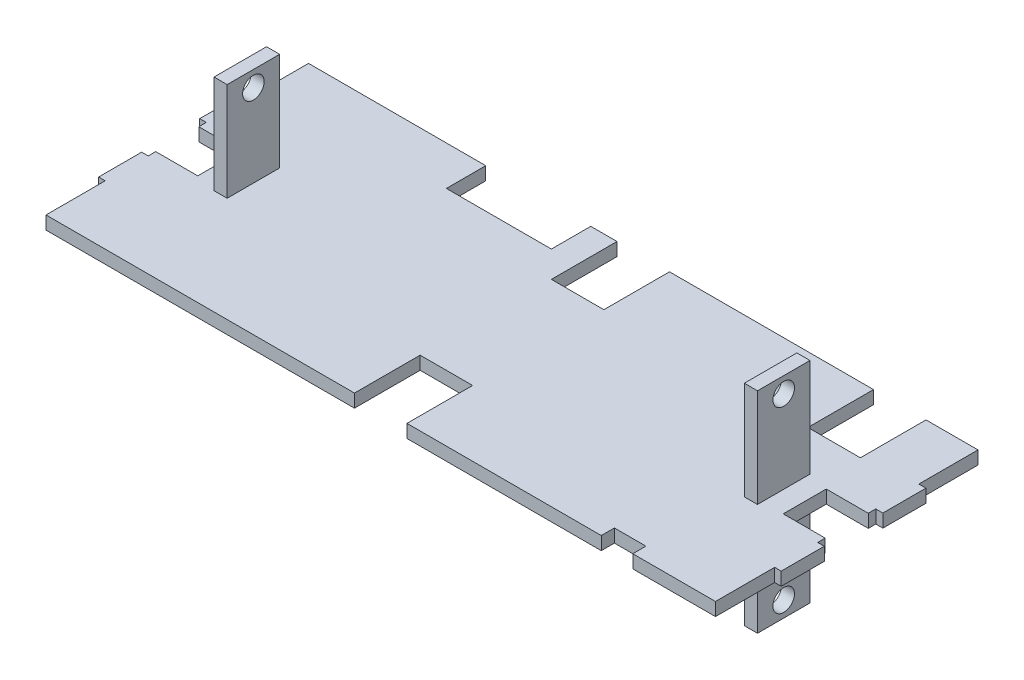
SolidWorks part; units mm, degrees
ref_plane "Front Plane" through (0, 0, 0) normal (0, 0, 1) x (1, 0, 0)
ref_plane "Top Plane" through (0, 0, 0) normal (0, 1, 0) x (1, 0, 0)
ref_plane "Right Plane" through (0, 0, 0) normal (1, 0, 0) x (0, 0, -1)
sketch "Sketch1" plane through (0, 0, 0) normal (0, 1, 0) x (1, 0, 0)
  line L0 (-136.779, 63.5) -> (-111.379, 63.5)
  line L1 (161.925, -63.5) -> (121.92, -63.5)
  line L2 (161.925, -63.5) -> (161.925, -34.8747)
  line L3 (161.925, 63.5) -> (136.779, 63.5)
  line L4 (-161.925, -63.5) -> (-161.925, -34.8747)
  line L5 (161.925, -63.5) -> (-161.925, 63.5) construction
  line L6 (161.925, 63.5) -> (-161.925, -63.5) construction
  line L7 (161.925, 10.414) -> (141.605, 10.414)
  line L9 (161.925, -10.414) -> (141.605, -10.414)
  line L10 (141.605, 10.414) -> (141.605, -10.414)
  line L11 (-136.779, 63.5) -> (-161.925, 63.5)
  line L13 (-161.925, -10.414) -> (-141.605, -10.414)
  line L14 (-141.605, 10.414) -> (-141.605, -10.414)
  line L15 (-161.925, 10.414) -> (-141.605, 10.414)
  line L17 (-141.605, 0) -> (127, 0) construction
  line L18 (-161.925, 14.0467) -> (-165.1, 14.0467)
  line L20 (-161.925, 34.8747) -> (-165.1, 34.8747)
  line L21 (-165.1, 14.0467) -> (-165.1, 34.8747)
  line L22 (-161.925, -34.8747) -> (-165.1, -34.8747)
  line L23 (-165.1, -14.0467) -> (-165.1, -34.8747)
  line L24 (-161.925, -14.0467) -> (-165.1, -14.0467)
  line L27 (161.925, -14.0467) -> (165.1, -14.0467)
  line L28 (165.1, -14.0467) -> (165.1, -34.8747)
  line L29 (161.925, -34.8747) -> (165.1, -34.8747)
  line L30 (161.925, 34.8747) -> (165.354, 34.8747)
  line L31 (165.354, 14.0467) -> (165.354, 34.8747)
  line L32 (161.925, 14.0467) -> (165.354, 14.0467)
  line L34 (-161.925, 34.8747) -> (-161.925, 63.5)
  line L35 (-161.925, -14.0467) -> (-161.925, -10.414)
  line L36 (161.925, 34.8747) -> (161.925, 63.5)
  line L37 (161.925, -14.0467) -> (161.925, -10.414)
  line L38 (-161.925, 10.414) -> (-161.925, 14.0467)
  line L39 (161.925, 10.414) -> (161.925, 14.0467)
  line L44 (111.379, 63.5) -> (111.379, 31.75)
  line L45 (111.379, 31.75) -> (136.779, 31.75)
  line L46 (136.779, 63.5) -> (136.779, 31.75)
  line L47 (111.379, 63.5) -> (12.7, 63.5)
  line L48 (106.68, -63.5) -> (12.7, -63.5)
  line L50 (106.68, -63.5) -> (106.68, -57.15)
  line L51 (106.68, -57.15) -> (121.92, -57.15)
  line L52 (121.92, -63.5) -> (121.92, -57.15)
  line L56 (-135.9408, -63.5) -> (-161.925, -63.5)
  line L57 (-106.68, -63.5) -> (-110.5408, -63.5)
  line L62 (-12.7, 63.5) -> (-111.379, 63.5)
  line L64 (12.7, 63.5) -> (12.7, 31.75)
  line L65 (12.7, 31.75) -> (-12.7, 31.75)
  line L66 (-12.7, 63.5) -> (-12.7, 31.75)
  line L67 (-135.9408, -63.5) -> (-110.5408, -63.5)
  line L68 (12.7, -63.5) -> (12.7, -31.75)
  line L69 (0, 31.75) -> (0, -63.5) construction
  line L70 (12.7, -31.75) -> (-12.7, -31.75)
  line L71 (-12.7, -63.5) -> (-12.7, -31.75)
  line L72 (-12.7, -63.5) -> (-106.68, -63.5)
  point P0 (0, 0)
  point P6 (141.605, 0)
  point P47 (121.92, -60.325)
  point P48 (124.079, 31.75)
  point P50 (0, 63.5)
  point P63 (0, 31.75)
  dimension "D1" = 323.85
  dimension "D2" = 127
  dimension "D3" = 20.828
  dimension "D5" = 3.175
  dimension "D6" = 20.828
  dimension "D4" = 20.32
  dimension "D9" = 25.4
  dimension "D10" = 31.75
  dimension "D13" = 15.24
  dimension "D14" = 6.35
  dimension "D15" = 40.005
  dimension "D11" = 41.275
  dimension "D19" = 31.75
  dimension "D20" = 25.4
extrude "Boss-Extrude1" add sketch "Sketch1" along normal mid plane 6.35
sketch "Sketch2" plane through (0, 0, 0) normal (0, 1, 0) x (1, 0, 0)
  line L0 (-141.605, 10.414) -> (-141.605, -10.414) construction
  line L1 (125.095, -12.7) -> (131.445, -12.7)
  line L2 (125.095, -12.7) -> (125.095, 12.7)
  line L3 (125.095, 12.7) -> (131.445, 12.7)
  line L4 (131.445, -12.7) -> (131.445, 12.7)
  line L5 (125.095, -12.7) -> (131.445, 12.7) construction
  line L6 (125.095, 12.7) -> (131.445, -12.7) construction
  line L9 (-125.095, -12.7) -> (-125.095, 12.7)
  line L10 (-125.095, 12.7) -> (-131.445, 12.7)
  line L11 (-131.445, -12.7) -> (-131.445, 12.7)
  line L12 (-125.095, -12.7) -> (-131.445, -12.7)
  line L13 (141.605, -10.414) -> (141.605, 10.414) construction
  point P0 (128.27, 0)
  point P10 (141.605, 0)
  dimension "D1" = 10.16
  dimension "D2" = 10.16
  dimension "D3" = 25.4
  dimension "D4" = 25.4
  dimension "D5" = 6.35
  dimension "D6" = 6.35
  dimension "D7" = 6.35
extrude "Boss-Extrude2" add sketch "Sketch2" along normal mid plane 101.6
sketch "Sketch3" plane through (-131.445, 0, 0) normal (-1, 0, 0) x (0, 0, 1)
  line L0 (-12.7, 50.8) -> (12.7, 50.8) construction
  line L1 (-12.7, -50.8) -> (12.7, -50.8) construction
  circle A0 centre (0, 43.18) radius 5.207
  circle A1 centre (0, -43.18) radius 5.207
  point P4 (0, 50.8)
  dimension "D1" = 10.414
  dimension "D2" = 10.414
  dimension "D3" = 7.62
  dimension "D4" = 7.62
  dimension "D5" = 86.36
extrude "Cut-Extrude1" cut sketch "Sketch3" against normal through all both and the other way through all
sketch "Sketch4" plane through (0, 3.175, 0) normal (0, 1, 0) x (1, 0, 0)
  line L0 (-12.7, 63.5) -> (-161.925, 63.5) construction
  line L1 (-25.4, 63.5) -> (-76.2, 63.5)
  line L2 (-25.4, 63.5) -> (-25.4, 44.45)
  line L3 (-25.4, 44.45) -> (-76.2, 44.45)
  line L4 (-76.2, 63.5) -> (-76.2, 44.45)
  line L5 (-12.7, 31.75) -> (-12.7, 63.5) construction
  dimension "D1" = 50.8
  dimension "D2" = 19.05
  dimension "D3" = 12.7
extrude "Cut-Extrude2" cut sketch "Sketch4" against normal through all
equation "\"length\"= 12.75"
equation "\"width\"=5"
equation "\"height\"= 0.25"
equation "\"D1@Sketch1\"=\"length\""
equation "\"D2@Sketch1\"=\"width\""
equation "\"eyebolt width\"= 0.82"
equation "\"eyebolt length\"= 0.8"
equation "\"D3@Sketch1\"=\"eyebolt width\""
equation "\"D4@Sketch1\"=\"eyebolt length\""
equation "\"lead screw holder height\"= 2.76"
equation "\"lead screw diameter\"=0.41"
equation "\"D1@Sketch3\"=\"lead screw diameter\""
equation "\"distance from holders to board\"=0.4"
equation "\"D2@Sketch3\"=\"lead screw diameter\""
equation "\"lead_screw_dist\"=3.4"
equation "\"D5@Sketch3\"=\"lead_screw_dist\""
